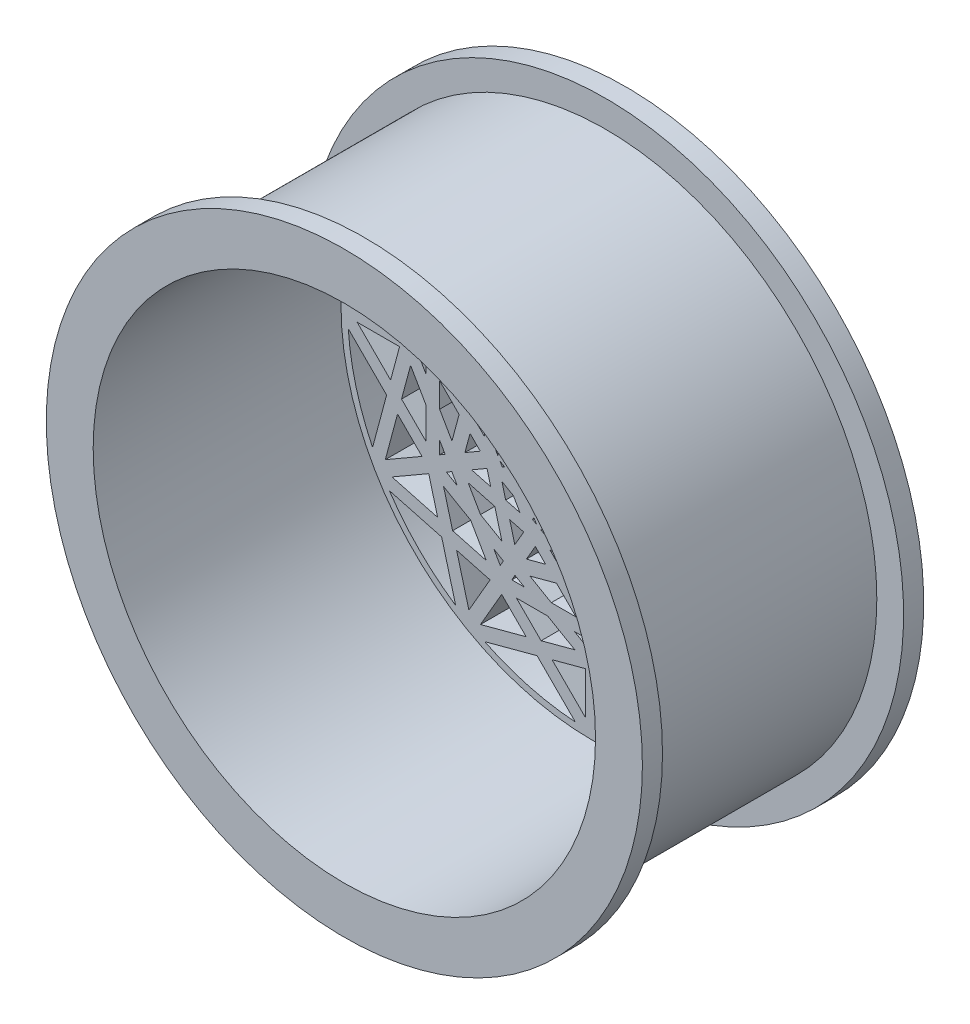
SolidWorks part; units mm, degrees
ref_plane "Front Plane" through (0, 0, 0) normal (0, 0, 1) x (1, 0, 0)
ref_plane "Top Plane" through (0, 0, 0) normal (0, 1, 0) x (1, 0, 0)
ref_plane "Right Plane" through (0, 0, 0) normal (1, 0, 0) x (0, 0, -1)
sketch "Sketch1" plane through (0, 0, 0) normal (0, 0, 1) x (1, 0, 0)
  circle A0 centre (0, 0) radius 40.5
  circle A1 centre (0, 0) radius 37.5
  dimension "D1" = 81
  dimension "D2" = 3
extrude "Boss-Extrude1" add sketch "Sketch1" along normal blind 36 contours A0 A1 region at (-39.3545, 0, 0)
sketch "Sketch2" plane through (0, 0, 0) normal (0, 0, -1) x (-1, 0, 0)
  circle A0 centre (0, 0) radius 40.5
  circle A1 centre (0, 0) radius 44.5
  circle A2 centre (0, 0) radius 40.5 construction
  circle M3 centre (0, 0) radius 37.5
  circle M4 centre (0, 0) radius 40.5
  dimension "D1" = 89
extrude "Boss-Extrude2" add sketch "Sketch2" along normal blind 3 contours A1 M4 | M3 | M4 M3 region at (39.3545, 0, 0) region at (43.2413, 0, 0) region at (0, 0, 0)
sketch "Sketch3" plane through (0, 0, 36) normal (0, 0, 1) x (1, 0, 0)
  circle A0 centre (0, 0) radius 37.5
  circle A1 centre (0, 0) radius 44.5
  circle A2 centre (0, 0) radius 37.5 construction
  dimension "D1" = 89
extrude "Boss-Extrude3" add sketch "Sketch3" along normal blind 3
sketch "Sketch4" plane through (0, 0, -3) normal (0, 0, -1) x (-1, 0, 0)
  circle A0 centre (0, 0) radius 5
  dimension "D1" = 10
extrude "Cut-Extrude1" cut sketch "Sketch4" against normal up to surface (3 mm away) up to face at (40.5, 0, 0)
sketch "Sketch5" plane through (0, 0, -3) normal (0, 0, -1) x (-1, 0, 0)
  circle A0 centre (0, 0) radius 37.5
  dimension "D1" = 75
extrude "Cut-Extrude2" cut sketch "Sketch5" against normal blind 1
sketch "Sketch6" plane through (0, 0, -2) normal (0, 0, -1) x (-1, 0, 0)
  line L0 (0, 0) -> (0, 37.5)
  line L1 (0, 0) -> (18.75, 32.476)
  line L2 (0, 0) -> (-18.75, 32.476)
  line L3 (-18.75, 32.476) -> (0, 27.4519)
  line L4 (0, 27.4519) -> (-11.887, 20.5889)
  line L5 (-11.887, 20.5889) -> (0, 17.4038)
  line L6 (0, 17.4038) -> (-7.5361, 13.0529)
  line L7 (-7.5361, 13.0529) -> (0, 11.0336)
  line L8 (0, 37.5) -> (-13.726, 23.774)
  line L9 (-13.726, 23.774) -> (0, 23.774)
  line L10 (0, 23.774) -> (-8.7019, 15.0721)
  line L11 (-8.7019, 15.0721) -> (0, 15.0721)
  line L12 (0, 15.0721) -> (-5.5168, 9.5554)
  line L13 (-16.0421, 32.7857) -> (-8.2235, 30.6907)
  line L14 (-8.2235, 30.6907) -> (-2.4999, 36.4143)
  line L15 (-16.6769, 30.8852) -> (-13.5115, 25.4027)
  line L16 (-13.5115, 25.4027) -> (-9.8565, 29.0577)
  line L17 (-9.8565, 29.0577) -> (-16.6769, 30.8852)
  line L18 (-5.9928, 30.093) -> (-1, 28.7551)
  line L19 (-1, 28.7551) -> (-1, 35.0858)
  line L20 (-1, 35.0858) -> (-5.9928, 30.093)
  line L21 (-11.3117, 24.774) -> (-7.6258, 28.46)
  line L22 (-7.6258, 28.46) -> (-2.5908, 27.1108)
  line L23 (-2.5908, 27.1108) -> (-6.6382, 24.774)
  line L24 (-6.6382, 24.774) -> (-11.3117, 24.774)
  line L25 (-11.9939, 22.774) -> (-11.521, 21.955)
  line L26 (-11.521, 21.955) -> (-10.1023, 22.774)
  line L27 (-10.1023, 22.774) -> (-11.9939, 22.774)
  line L28 (-1, 25.7199) -> (-2.6382, 24.774)
  line L29 (-2.6382, 24.774) -> (-1, 24.774)
  line L30 (-1, 24.774) -> (-1, 25.7199)
  line L31 (-9.2963, 20.93) -> (-6.1023, 22.774)
  line L32 (-6.1023, 22.774) -> (-2.4142, 22.774)
  line L33 (-2.4142, 22.774) -> (-5.3229, 19.8654)
  line L34 (-5.3229, 19.8654) -> (-9.2963, 20.93)
  line L35 (-9.8139, 18.9982) -> (-8.4875, 16.7008)
  line L36 (-8.4875, 16.7008) -> (-6.9559, 18.2324)
  line L37 (-6.9559, 18.2324) -> (-9.8139, 18.9982)
  line L38 (-3.0922, 19.2676) -> (-1, 18.707)
  line L39 (-1, 18.707) -> (-1, 21.3598)
  line L40 (-1, 21.3598) -> (-3.0922, 19.2676)
  line L41 (-4.7252, 17.6346) -> (-6.2877, 16.0721)
  line L42 (-6.2877, 16.0721) -> (-4.3065, 16.0721)
  line L43 (-4.3065, 16.0721) -> (-2.5908, 17.0627)
  line L44 (-2.5908, 17.0627) -> (-4.7252, 17.6346)
  line L45 (-6.9699, 14.0721) -> (-7.17, 14.4189)
  line L46 (-7.17, 14.4189) -> (-7.7706, 14.0721)
  line L47 (-7.7706, 14.0721) -> (-6.9699, 14.0721)
  line L48 (-4.9453, 13.3939) -> (-3.484, 13.0024)
  line L49 (-3.484, 13.0024) -> (-2.4142, 14.0721)
  line L50 (-2.4142, 14.0721) -> (-3.7706, 14.0721)
  line L51 (-3.7706, 14.0721) -> (-4.9453, 13.3939)
  line L52 (-1, 15.6718) -> (-1, 16.0721)
  line L53 (-1, 16.0721) -> (-0.3065, 16.0721)
  line L54 (-0.3065, 16.0721) -> (-1, 15.6718)
  line L55 (-1, 12.6579) -> (-1.2533, 12.4047)
  line L56 (-1.2533, 12.4047) -> (-1, 12.3368)
  line L57 (-1, 12.3368) -> (-1, 12.6579)
  line L58 (-2.8863, 10.7717) -> (-3.1054, 10.5526)
  line L59 (-2.8863, 10.7717) -> (-2.587, 10.6915)
  line L60 (-5.4629, 11.4621) -> (-5.3024, 11.184)
  line L61 (-5.3024, 11.184) -> (-5.117, 11.3694)
  line L62 (-5.117, 11.3694) -> (-5.4629, 11.4621)
  circle A0 centre (0, 0) radius 37.5 construction
  circle A1 centre (0, 0) radius 11
  circle A2 centre (0, 0) radius 5 construction
  circle A3 centre (0, 0) radius 36.5
  circle M67 centre (0, 0) radius 37.5
  circle M68 centre (0, 0) radius 5
  dimension "D1" = 30
  dimension "D2" = 6
  dimension "D3" = 45
  dimension "D4" = 45
  dimension "D5" = 1
  dimension "D6" = 1
  dimension "D7" = 1
  dimension "D8" = 1
  dimension "D9" = 1
  dimension "D10" = 1
  dimension "D11" = 1
  dimension "D12" = 1
  dimension "D13" = 1
  dimension "D14" = 1
  dimension "D15" = 1
  dimension "D16" = 1
  dimension "D17" = 1
  dimension "D18" = 1
  dimension "D19" = 1
  dimension "D20" = 1
  dimension "D21" = 1
  dimension "D22" = 1
  dimension "D23" = 1
  dimension "D24" = 1
  dimension "D25" = 1
  dimension "D26" = 1
  dimension "D27" = 1
  dimension "D28" = 1
  dimension "D29" = 1
  dimension "D30" = 1
  dimension "D31" = 1
  dimension "D32" = 1
  dimension "D33" = 1
  dimension "D34" = 1
  dimension "D35" = 1
  dimension "D36" = 1
  dimension "D37" = 1
  dimension "D38" = 1
  dimension "D39" = 1
  dimension "D40" = 1
  dimension "D41" = 1
  dimension "D42" = 1
  dimension "D43" = 1
  dimension "D44" = 1
  dimension "D45" = 1
  dimension "D46" = 1
  dimension "D47" = 1
  dimension "D48" = 1
  dimension "D49" = 1
  dimension "D50" = 1
  dimension "D51" = 1
  dimension "D52" = 1
  dimension "D53" = 1
extrude "Cut-Extrude3" cut sketch "Sketch6" against normal up to surface (2 mm away) contours L14 A3 L13 | L16 L17 L15 | L19 L20 L18 | L24 L23 L22 L21 | L29 L30 L28 | L26 L27 L25 | L34 L33 L32 L31 | L36 L37 L35 | L39 L40 L38 | L43 L44 L41 L42 | L50 L51 L48 L49 | L56 L57 L55 | L61 L62 L60 | A1 L59 L58 region at (2.8599, 10.6733, -2) region at (8.9987, 33.5837, -2) region at (13.3483, 28.4485, -2) region at (2.6643, 31.3113, -2) region at (7.0718, 26.3921, -2) region at (11.2057, 22.501, -2) region at (1.5461, 25.0893, -2) region at (5.7601, 21.4971, -2) region at (8.4191, 17.9771, -2) region at (1.6974, 19.7782, -2) region at (4.4903, 16.7581, -2) region at (3.6448, 13.6025, -2) region at (1.0844, 12.4665, -2) region at (5.2941, 11.3385, -2) up to face at (-5, 0, 0)
pattern_circular "CirPattern1" count 12 every 30 about axis through (0, 0, -2) along (0, 0, 1) of "Cut-Extrude3"
extrude "Boss-Extrude4" add sketch "Sketch6<4>" along normal up to surface (1 mm away) and the other way blind 4 contours A3 L8 L3 M67 | A3 L0 L8 | A3 L3 L2 | L3 A3 L2 L8 L17 L16 L15 | L8 A3 L14 L13 L3 | L0 A3 L8 L3 L20 L19 L18 | L8 L9 L4 L3 L23 L24 L21 L22 | L9 L2 L4 L27 L26 L25 | L4 L9 L0 L30 L29 L28 | L10 L9 L4 L5 L33 L34 L31 L32 | L0 L10 L5 L40 L39 L38 | L10 L5 L2 L37 L36 L35 | L10 L11 L6 L5 L44 L43 L42 L41 | L6 L11 L0 L53 L54 L52 | L11 L2 L6 L47 L46 L45 | L12 L11 L6 L7 L51 L50 L49 L48 | L0 L12 L7 L57 L56 L55 | L12 L7 L2 L62 L61 L60 | A1 L0 L7 L12 L2 L58 L59 | L0 A1 L2 M68 region at (1.0616, 12.6655, -2) region at (2.9398, 10.9715, -2) region at (1.3637, 15.8467, -2) region at (1.6504, 13.5374, -2) region at (2.1429, 7.9975, -2) region at (5.4134, 11.4994, -2) region at (2.491, 18.1553, -2) region at (2.0665, 16.3198, -2) region at (6.7423, 14.4055, -2) region at (3.1851, 23.8476, -2) region at (2.6033, 21.3533, -2) region at (6.9252, 16.9733, -2) region at (3.9312, 28.6298, -2) region at (3.2596, 25.742, -2) region at (9.1687, 22.2509, -2) region at (0.3372, 36.8302, -2) region at (10.9191, 26.7685, -2) region at (12.5988, 31.0115, -2) region at (9.4809, 35.3833, -2) region at (18.1231, 32.0645, -2) up to face at (-37.5, 0, -3)
sketch "Sketch6<4>" plane through (0, 0, -2) normal (0, 0, -1) x (-1, 0, 0) same geometry as "Sketch6"
pattern_circular "CirPattern2" count 12 every 30 about axis through (0, 0, -3) along (0, 0, -1) of "Boss-Extrude4"
sketch "Sketch7" plane through (0, 0, -3) normal (0, 0, -1) x (-1, 0, 0)
  line L0 (0, 0) -> (0, 8.9745)
  line L1 (0, 0) -> (-2.0706, 7.7274)
  circle A0 centre (0, 0) radius 5.5
  circle A1 centre (-2.0706, 7.7274) radius 1.5
  circle A2 centre (5.6569, 5.6569) radius 1.5
  circle A3 centre (7.7274, -2.0706) radius 1.5
  circle A4 centre (2.0706, -7.7274) radius 1.5
  circle A5 centre (-5.6569, -5.6569) radius 1.5
  circle A6 centre (-7.7274, 2.0706) radius 1.5
  point P19 (0, 0)
  dimension "D1" = 3
  dimension "D2" = 11
  dimension "D3" = 8
  dimension "D4" = 15
  dimension "D5" = 6
extrude "Cut-Extrude4" cut sketch "Sketch7" against normal up to surface (5 mm away) contours A1 | A2 | A3 | A4 | A5 | A6 | L1 A0 L0 | L0 A0 L1 region at (0.4772, 3.6249, -3) region at (-0.0207, -0.1576, -3) region at (3.2269, 8.6147, -3) region at (-5.6569, 5.6569, -3) region at (-7.7274, -2.0706, -3) region at (-2.0706, -7.7274, -3) region at (5.6569, -5.6569, -3) region at (7.7274, 2.0706, -3) up to face at (-37.5, 0, 2)
ref_plane "Plane1" through (0, 0, -0.5) normal (0, 0, -1) x (-1, 0, 0)
sketch "Sketch10" plane through (0, 0, -3) normal (0, 0, -1) x (-1, 0, 0)
  line L0 (0, 0) -> (0, 36.5)
  circle A0 centre (0, 0) radius 36.5
  arc A1 (-2.4999, 36.4143) -> (-16.0421, 32.7857) centre (0, 0) ccw construction
  point P6 (0, 0)
sketch3d "3DSketch3"
  line L0 (0, 0, -0.5) -> (0, 0, -535.9)
  circle A0 centre (0, 0, -3) radius 5.5 construction
  arc A1 (0, 0, -0.5) -> (0, 0, -535.9) centre (0, 0, -268.2) cw
  point P2 (0, 0, 0)
  point P5 (0, 0, -8.5)
  point P8 (-267.7, 0, -268.2)
sweep "Cut-Sweep4" cut profiles "3DSketch3" path "Sketch10"
equation "\"spokewidth\"=1"
equation "\"D6@Sketch6\"=\"spokewidth\""
equation "\"D7@Sketch6\"=\"spokewidth\""
equation "\"D8@Sketch6\"=\"spokewidth\""
equation "\"D9@Sketch6\"=\"spokewidth\""
equation "\"D10@Sketch6\"=\"spokewidth\""
equation "\"D11@Sketch6\"=\"spokewidth\""
equation "\"D12@Sketch6\"=\"spokewidth\""
equation "\"D13@Sketch6\"=\"spokewidth\""
equation "\"D14@Sketch6\"=\"spokewidth\""
equation "\"D15@Sketch6\"=\"spokewidth\""
equation "\"D16@Sketch6\"=\"spokewidth\""
equation "\"D17@Sketch6\"=\"spokewidth\""
equation "\"D18@Sketch6\"=\"spokewidth\""
equation "\"D19@Sketch6\"=\"spokewidth\""
equation "\"D20@Sketch6\"=\"spokewidth\""
equation "\"D21@Sketch6\"=\"spokewidth\""
equation "\"D22@Sketch6\"=\"spokewidth\""
equation "\"D23@Sketch6\"=\"spokewidth\""
equation "\"D24@Sketch6\"=\"spokewidth\""
equation "\"D25@Sketch6\"=\"spokewidth\""
equation "\"D26@Sketch6\"=\"spokewidth\""
equation "\"D27@Sketch6\"=\"spokewidth\""
equation "\"D28@Sketch6\"=\"spokewidth\""
equation "\"D29@Sketch6\"=\"spokewidth\""
equation "\"D30@Sketch6\"=\"spokewidth\""
equation "\"D31@Sketch6\"=\"spokewidth\""
equation "\"D32@Sketch6\"=\"spokewidth\""
equation "\"D33@Sketch6\"=\"spokewidth\""
equation "\"D34@Sketch6\"=\"spokewidth\""
equation "\"D35@Sketch6\"=\"spokewidth\""
equation "\"D36@Sketch6\"=\"spokewidth\""
equation "\"D37@Sketch6\"=\"spokewidth\""
equation "\"D38@Sketch6\"=\"spokewidth\""
equation "\"D39@Sketch6\"=\"spokewidth\""
equation "\"D40@Sketch6\"=\"spokewidth\""
equation "\"D41@Sketch6\"=\"spokewidth\""
equation "\"D42@Sketch6\"=\"spokewidth\""
equation "\"D43@Sketch6\"=\"spokewidth\""
equation "\"D44@Sketch6\"=\"spokewidth\""
equation "\"D45@Sketch6\"=\"spokewidth\""
equation "\"D46@Sketch6\"=\"spokewidth\""
equation "\"D47@Sketch6\"=\"spokewidth\""
equation "\"D48@Sketch6\"=\"spokewidth\""
equation "\"D49@Sketch6\"=\"spokewidth\""
equation "\"D50@Sketch6\"=\"spokewidth\""
equation "\"D51@Sketch6\"=\"spokewidth\""
equation "\"D52@Sketch6\"=\"spokewidth\""
equation "\"D53@Sketch6\"=\"spokewidth\""
